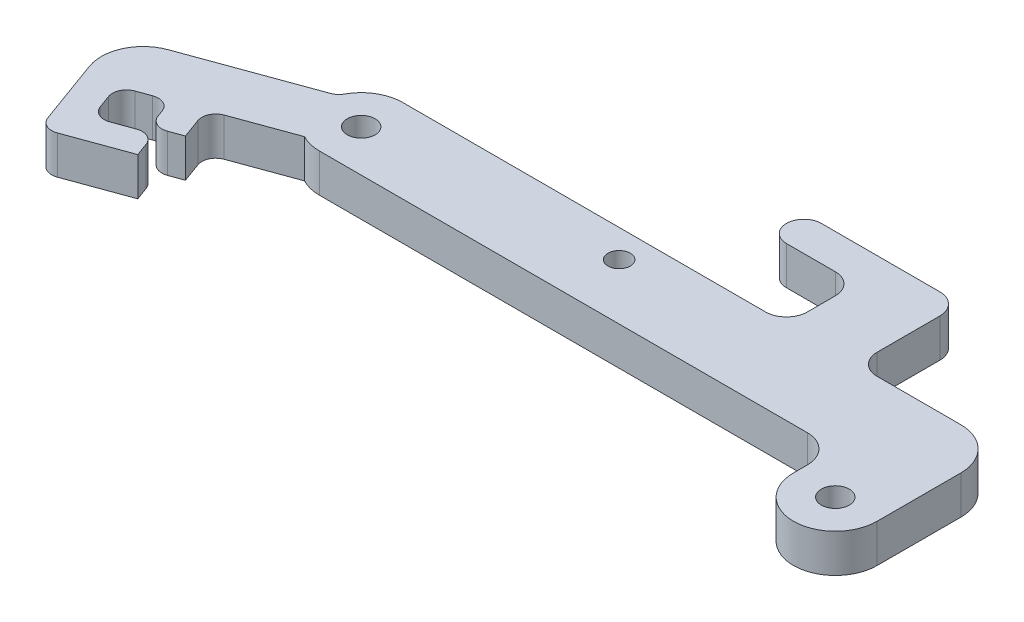
SolidWorks part; units mm, degrees
ref_plane "正面" through (0, 0, 0) normal (0, 0, 1) x (1, 0, 0)
ref_plane "平面" through (0, 0, 0) normal (0, 1, 0) x (1, 0, 0)
ref_plane "右側面" through (0, 0, 0) normal (1, 0, 0) x (0, 0, -1)
sketch "ｽｹｯﾁ1" plane through (0, 0, 0) normal (0, 1, 0) x (1, 0, 0)
  line L0 (0, 0) -> (80, 0) construction
  line L1 (0, 6) -> (80, 6)
  line L2 (0, -6) -> (80, -6)
  arc A0 (0, 6) -> (0, -6) centre (0, 0) ccw
  arc A1 (80, -6) -> (80, 6) centre (80, 0) ccw
  circle A2 centre (0, 0) radius 2
  circle A3 centre (80, 0) radius 2 construction
  circle A4 centre (64, 3.3) radius 1.25 construction
  point P3 (40, 0)
  dimension "D2" = 6
  dimension "D3" = 4
  dimension "D4" = 4
  dimension "D7" = 2.5
  dimension "D1" = 80
  dimension "D5" = 64
  dimension "D6" = 2.7
extrude "ﾎﾞｽ - 押し出し1" add sketch "ｽｹｯﾁ1" along normal blind 5.5
sketch "ｽｹｯﾁ3" plane through (0, 5.5, 0) normal (0, 1, 0) x (1, 0, 0)
  line L0 (80, 0) -> (80, -12) construction
  line L1 (86, 0) -> (86, -12)
  line L2 (74, 0) -> (74, -12)
  line L3 (0, -6) -> (80, -6) construction
  arc A0 (86, 0) -> (74, 0) centre (80, 0) ccw
  arc A1 (74, -12) -> (86, -12) centre (80, -12) ccw
  arc A2 (80, -6) -> (80, 6) centre (80, 0) ccw construction
  circle A3 centre (80, -12) radius 2
  point P3 (80, -6)
  dimension "D1" = 4
extrude "ﾎﾞｽ - 押し出し3" add sketch "ｽｹｯﾁ3" against normal up to surface (5.5 mm away) up to face at (40, 0, 0)
fillet "ﾌｨﾚｯﾄ1" radius 4 1 edges at (74, 2.75, 6)
sketch "ｽｹｯﾁ4" plane through (0, 5.5, 0) normal (0, 1, 0) x (1, 0, 0)
  line L1 (80, 6) -> (0, 6) construction
  circle A0 centre (35, 2) radius 1.6
  circle A1 centre (80, -12) radius 2 construction
  dimension "D1" = 3.2
  dimension "D2" = 45
  dimension "D3" = 4
extrude "ｶｯﾄ - 押し出し1" cut sketch "ｽｹｯﾁ4" against normal blind 10
sketch "ｽｹｯﾁ6" plane through (0, 0, 0) normal (0, -1, 0) x (1, 0, 0)
  line L0 (78.8097, 17.8807) -> (125.9619, 65.033)
  line L1 (125.9619, 65.033) -> (140.1041, 50.8909)
  line L2 (85.8807, 10.8097) -> (118.8909, 43.8198)
  line L3 (129.4975, 54.4264) -> (136.5685, 47.3553)
  line L4 (129.4975, 54.4264) -> (122.4264, 61.4975) construction
  line L5 (78.8097, 17.8807) -> (84.2426, 16.2426)
  line L6 (133.033, 57.9619) -> (129.4975, 54.4264) construction
  line L7 (84.2426, 16.2426) -> (85.8807, 10.8097)
  line L8 (86, 0) -> (86, 12) construction
  line L9 (125.9619, 57.9619) -> (80, 12) construction
  line L10 (118.8909, 43.8198) -> (125.9619, 36.7487)
  line L11 (129.4975, 40.2843) -> (122.4264, 47.3553)
  line L12 (122.4264, 47.3553) -> (129.4975, 54.4264)
  arc A0 (86, 12) -> (74, 12) centre (80, 12) ccw construction
  arc A1 (136.5685, 47.3553) -> (140.1041, 50.8909) centre (138.3363, 49.1231) ccw
  arc A3 (125.9619, 36.7487) -> (129.4975, 40.2843) centre (127.7297, 38.5165) ccw
  dimension "D1" = 10
  dimension "D2" = 50
  dimension "D3" = 20
  dimension "D4" = 135
  dimension "D5" = 5
  dimension "D7" = 10
  dimension "D6" = 2
extrude "ﾎﾞｽ - 押し出し4" [suppressed] add sketch "ｽｹｯﾁ6" against normal up to surface (5.5 mm away) up to face at (35, 5.5, -0.4)
fillet "ﾌｨﾚｯﾄ2" [suppressed] radius 3
sketch "ｽｹｯﾁ7" plane through (0, 5.5, 0) normal (0, 1, 0) x (1, 0, 0)
  line L0 (55, 6) -> (55, 16)
  line L1 (80, 6) -> (0, 6) construction
  line L2 (55, 16) -> (45, 16)
  line L3 (45, 21) -> (65, 21)
  line L4 (65, 21) -> (65, 6)
  line L5 (55, 6) -> (65, 6)
  arc A0 (45, 16) -> (45, 21) centre (45, 18.5) cw
  circle A1 centre (80, -12) radius 2 construction
  point P11 (60, 6)
  dimension "D5" = 20
  dimension "D1" = 10
  dimension "D2" = 5
  dimension "D3" = 10
  dimension "D4" = 10
extrude "ﾎﾞｽ - 押し出し5" add sketch "ｽｹｯﾁ7" against normal up to surface (5.5 mm away) up to face at (35, 0, -0.4)
fillet "ﾌｨﾚｯﾄ3" radius 3 4 edges at (65, 2.75, -6) (65, 2.75, -21) (55, 2.75, -16) (55, 2.75, -6)
sketch "ｽｹｯﾁ8" plane through (0, 5.5, 0) normal (0, 1, 0) x (1, 0, 0)
  line L10 (-5.5705, 2.2292) -> (-23.4247, -4.2692)
  line L11 (-27.0107, -11.9594) -> (-22.9065, -23.2358)
  line L13 (-20.5158, -18.1089) -> (-22.5679, -12.4708)
  line L14 (-22.5679, -12.4708) -> (-16.9297, -10.4186)
  line L15 (-16.9297, -10.4186) -> (-15.2196, -15.1171)
  line L16 (-15.2196, -15.1171) -> (-11.4609, -13.749)
  line L17 (-11.4609, -13.749) -> (-13.171, -9.0506)
  line L18 (-13.171, -9.0506) -> (-2.8344, -5.2883)
  line L19 (-16.9297, -10.4186) -> (-19.6659, -2.9011) construction
  line L20 (-18.2978, -6.6599) -> (0, 0) construction
  line L21 (0, -6) -> (70, -6) construction
  line L22 (-20.5158, -18.1089) -> (-13.9379, -15.7148)
  line L23 (-13.9379, -15.7148) -> (-12.5698, -19.4735)
  line L24 (-12.5698, -19.4735) -> (-22.9065, -23.2358)
  arc A0 (-5.5705, 2.2292) -> (-2.8344, -5.2883) centre (0, 0) ccw
  arc A4 (0, 6) -> (0, -6) centre (0, 0) ccw construction
  arc A5 (-23.4247, -4.2692) -> (-27.0107, -11.9594) centre (-21.3726, -9.9073) ccw
  point P21 (-29.0628, -6.3213)
  point P25 (-22.981, -22.8863)
  dimension "D7" = 6
  dimension "D1" = 4
  dimension "D2" = 6
  dimension "D3" = 25
  dimension "D4" = 8
  dimension "D5" = 6
  dimension "D6" = 160
  dimension "D8" = 4
  dimension "D9" = 11
  dimension "D10" = 5
  dimension "D11" = 4
extrude "ﾎﾞｽ - 押し出し6" add sketch "ｽｹｯﾁ8" against normal up to surface (5.5 mm away) up to face at (35, 0, -0.4)
fillet "ﾌｨﾚｯﾄ4" radius 2 8 edges at (-16.9297, 2.75, 10.4186) (-22.5679, 2.75, 12.4708) (-13.171, 2.75, 9.0506) (-5.5705, 2.75, -2.2292) (-15.2196, 2.75, 15.1171) (-13.9379, 2.75, 15.7148) (-20.5158, 2.75, 18.1089) (-22.9065, 2.75, 23.2358)
